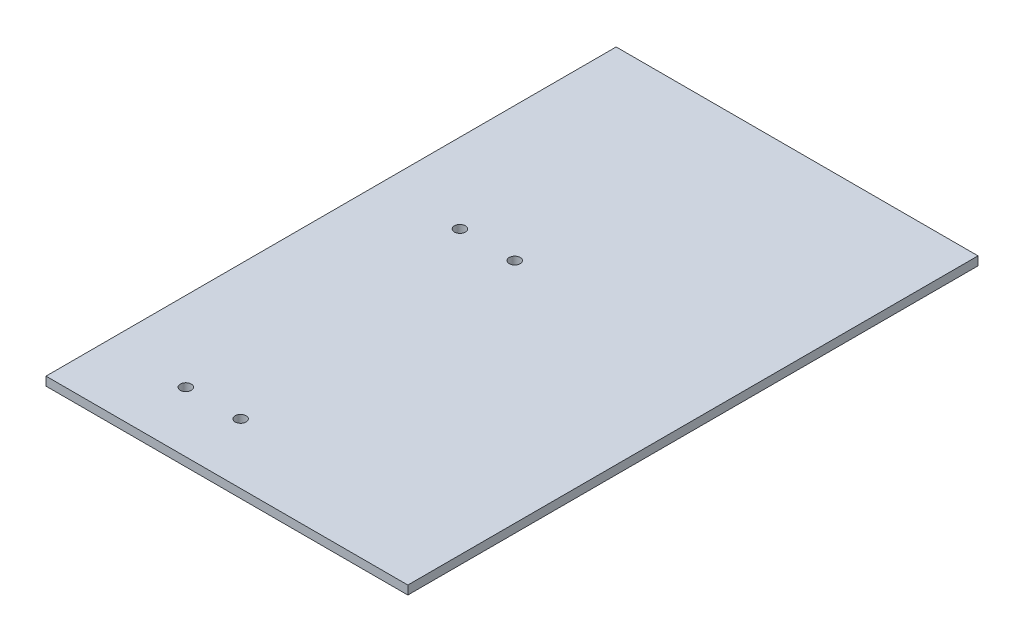
SolidWorks part; units mm, degrees
material "Alliage 1060"
ref_plane "Plan de face" through (0, 0, 0) normal (0, 0, 1) x (1, 0, 0)
ref_plane "Plan de dessus" through (0, 0, 0) normal (0, 1, 0) x (1, 0, 0)
ref_plane "Plan de droite" through (0, 0, 0) normal (1, 0, 0) x (0, 0, -1)
sketch "Esquisse1" plane through (0, 0, 0) normal (0, 1, 0) x (1, 0, 0)
  line L1 (-33, -52) -> (33, -52)
  line L2 (-33, -52) -> (-33, 52)
  line L3 (-33, 52) -> (33, 52)
  line L4 (33, -52) -> (33, 52)
  line L5 (-33, -52) -> (33, 52) construction
  line L6 (-33, 52) -> (33, -52) construction
  point P0 (0, 0)
  dimension "D1" = 104
  dimension "D2" = 66
extrude "Boss.-Extru.1" add sketch "Esquisse1" along normal blind 1.5875
sketch "Esquisse2" plane through (-33, 0, 0) normal (-1, 0, 0) x (0, 0, 1)
  line L1 (-52, 0) -> (52, 0)
  line L2 (-52, 0) -> (-52, 4)
  line L3 (-52, 4) -> (52, 4)
  line L4 (52, 0) -> (52, 4)
  dimension "D1" = 4
  dimension "D2" = 104
extrude "Boss.-Extru.2" [suppressed] add sketch "Esquisse2" along normal blind 1.5875 contours L3 L4 L1 L2
sketch "Esquisse3" plane through (33, 0, 0) normal (1, 0, 0) x (0, 0, -1)
  line L1 (-52, 0) -> (52, 0)
  line L2 (-52, 0) -> (-52, 4)
  line L3 (-52, 4) -> (52, 4)
  line L4 (52, 0) -> (52, 4)
  dimension "D1" = 104
  dimension "D2" = 4
extrude "Boss.-Extru.3" [suppressed] add sketch "Esquisse3" along normal blind 1.5875
fillet "Congé2" [suppressed] radius 2 type face fillet
fillet "Congé3" [suppressed] radius 2 type face fillet
sketch "Esquisse4" plane through (0, 1.5875, 0) normal (0, 1, 0) x (1, 0, 0)
  line L0 (-33, 52) -> (-33, -52) construction
  line L1 (-8.5, -41) -> (-18.5, -41) construction
  line L2 (-8.5, -41) -> (-8.5, 9) construction
  line L3 (-8.5, 9) -> (-18.5, 9) construction
  line L4 (-18.5, -41) -> (-18.5, 9) construction
  line L6 (-33, -52) -> (33, -52) construction
  line L8 (-8.5, -41) -> (-18.5, 9) construction
  line L9 (-18.5, -41) -> (-8.5, 9) construction
  circle A0 centre (-18.5, 9) radius 1
  circle A1 centre (-8.5, 9) radius 1
  circle A2 centre (-8.5, -41) radius 1
  circle A3 centre (-18.5, -41) radius 1
  dimension "D5" = 2
  dimension "D1" = 50
  dimension "D2" = 10
  dimension "D3" = 14.5
  dimension "D4" = 11
extrude "Enlèv. mat.-Extru.1" cut sketch "Esquisse4" against normal blind 1.5875 contours A0 | A1 | A3 | A2
